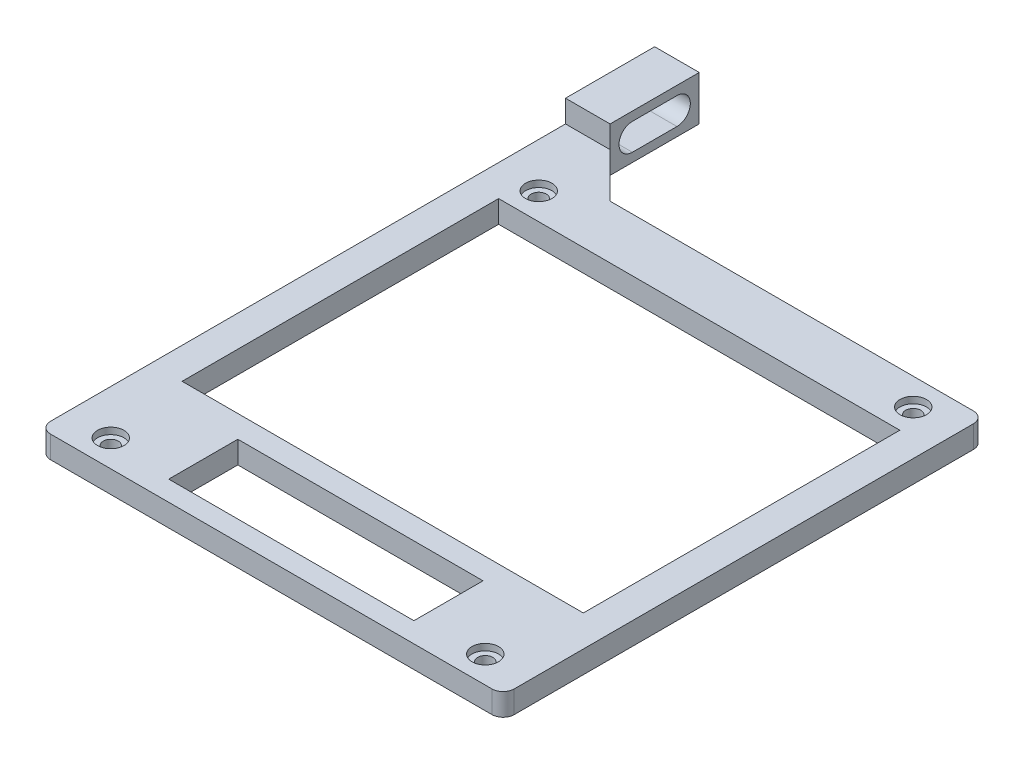
SolidWorks part; units mm, degrees
ref_plane "Front Plane" through (0, 0, 0) normal (0, 0, 1) x (1, 0, 0)
ref_plane "Top Plane" through (0, 0, 0) normal (0, 1, 0) x (1, 0, 0)
ref_plane "Right Plane" through (0, 0, 0) normal (1, 0, 0) x (0, 0, -1)
sketch "Sketch1" plane through (0, 0, 0) normal (0, 1, 0) x (1, 0, 0)
  line L1 (0, 0) -> (132.08, 0)
  line L2 (0, 0) -> (0, 137.16)
  line L3 (0, 137.16) -> (132.08, 137.16)
  line L4 (132.08, 0) -> (132.08, 137.16)
  dimension "D1" = 132.08
  dimension "D2" = 137.16
extrude "Boss-Extrude1" add sketch "Sketch1" along normal blind 6.35
ref_axis "Axis1" through (66.04, 6.35, 0) along (0, 0, -1)
ref_axis "Axis2" through (0, 6.35, -68.58) along (1, 0, 0)
hole_wizard "CBORE for #6 Button Head Cap Screw1" positions "Sketch4" profile "Sketch3" counterbore size "#6" standard "ANSI Inch" end condition up to next
sketch "Sketch4" plane through (0, 6.35, 0) normal (0, 1, 0) x (1, 0, 0)
  line L0 (12.7, 129.54) -> (119.38, 129.54)
  line L1 (119.38, 129.54) -> (119.38, 7.62)
  line L2 (119.38, 7.62) -> (12.7, 7.62)
  line L4 (12.7, 129.54) -> (12.7, 7.62)
  line L7 (66.04, 0) -> (66.04, 137.16) construction
  line L8 (0, 68.58) -> (132.08, 68.58) construction
  point P0 (12.7, 129.54)
  point P2 (119.38, 129.54)
  point P4 (119.38, 7.62)
  point P6 (12.7, 7.62)
  point P28 (66.04, 129.54)
  point P31 (119.38, 68.58)
  dimension "D1" = 106.68
  dimension "D2" = 121.92
sketch "Sketch3" plane through (12.7, 6.35, -129.54) normal (1, 0, 0) x (0, 0, 1)
  line L0 (0, 0) -> (0, 6.35)
  line L1 (0, 6.35) -> (2.1526, 6.35)
  line L3 (2.1526, 6.35) -> (2.1527, 1.8542)
  line L4 (2.1527, 1.8542) -> (3.7706, 1.8542)
  line L5 (3.7706, 1.8542) -> (3.7706, 0)
  line L7 (3.7706, 0) -> (0, 0)
  line L11 (0, -6.35) -> (0, 107.95) construction
  dimension "Thru Hole Dia." = 4.3053
  dimension "Thru Hole Depth" = 6.35
  dimension "C'Bore Dia." = 7.5413
  dimension "C'Bore Depth" = 1.8542
sketch "Sketch5" plane through (0, 6.35, 0) normal (0, 1, 0) x (1, 0, 0)
  line L0 (0, 68.58) -> (132.08, 68.58) construction
  line L1 (8.89, 15.24) -> (123.19, 15.24)
  line L2 (8.89, 15.24) -> (8.89, 121.92)
  line L3 (8.89, 121.92) -> (123.19, 121.92)
  line L4 (123.19, 15.24) -> (123.19, 121.92)
  line L5 (8.89, 15.24) -> (123.19, 121.92) construction
  line L6 (8.89, 121.92) -> (123.19, 15.24) construction
  line L7 (66.04, 0) -> (66.04, 137.16) construction
  point P0 (66.04, 68.58)
  dimension "D1" = 114.3
  dimension "D2" = 106.68
extrude "Cut-Extrude1" cut sketch "Sketch5" against normal through all
sketch "Sketch6" plane through (0, 0, 0) normal (0, -1, 0) x (-1, 0, 0)
  line L1 (0, 137.16) -> (-12.7, 137.16)
  line L2 (0, 137.16) -> (0, 175.26)
  line L3 (0, 175.26) -> (-12.7, 175.26)
  line L4 (-12.7, 137.16) -> (-12.7, 175.26)
  dimension "D1" = 12.7
  dimension "D2" = 38.1
extrude "Boss-Extrude2" add sketch "Sketch6" against normal blind 6.35
sketch "Sketch7" plane through (0, 0, -175.26) normal (0, 0, -1) x (-1, 0, 0)
  line L4 (0, 6.35) -> (-12.7, 6.35)
  line L5 (0, 6.35) -> (0, 12.7)
  line L6 (0, 12.7) -> (-12.7, 12.7)
  line L7 (-12.7, 6.35) -> (-12.7, 12.7)
  dimension "D1" = 6.35
extrude "Boss-Extrude3" add sketch "Sketch7" against normal blind 25.4
sketch "Sketch8" plane through (0, 0, 0) normal (-1, 0, 0) x (0, 0, 1)
  line L0 (-175.26, 6.35) -> (-149.86, 6.35)
  line L1 (-175.26, 12.7) -> (-175.26, 0) construction
  line L3 (-168.91, 6.35) -> (-156.21, 6.35) construction
  line L4 (-168.91, 10.16) -> (-156.21, 10.16)
  line L5 (-168.91, 2.54) -> (-156.21, 2.54)
  arc A0 (-168.91, 10.16) -> (-168.91, 2.54) centre (-168.91, 6.35) ccw
  arc A1 (-156.21, 2.54) -> (-156.21, 10.16) centre (-156.21, 6.35) ccw
  point P8 (-162.56, 6.35)
  dimension "D1" = 3.81
  dimension "D2" = 6.35
extrude "Cut-Extrude2" cut sketch "Sketch8" against normal up to next contours L5 A1 L0 A0 | L0 A1 L4 A0 region at (0, 8.1628, -162.56) region at (0, 4.5372, -162.56)
ref_axis "Axis3" through (12.7, 6.35, -162.56) along (-1, 0, 0)
ref_axis "Axis4" through (12.7, 6.35, -156.21) along (-1, 0, 0)
chamfer "Chamfer1" distance 12.7 angle 45 1 edges at (12.7, 3.175, -137.16)
sketch "Sketch9" plane through (0, 6.35, 0) normal (0, 1, 0) x (1, 0, 0)
  line L7 (66.04, 15.24) -> (66.04, 0) construction
  line L8 (8.89, 15.24) -> (123.19, 15.24) construction
  line L9 (0, 0) -> (132.08, 0) construction
  line L10 (100.965, 15.24) -> (31.115, 15.24)
  line L11 (31.115, 15.24) -> (31.115, 5.715)
  line L12 (31.115, 5.715) -> (100.965, 5.715)
  line L13 (100.965, 15.24) -> (100.965, 5.715)
  point P10 (66.04, 5.715)
  dimension "D1" = 34.925
  dimension "D2" = 9.525
extrude "Cut-Extrude3" cut sketch "Sketch9" against normal up to next
fillet "Fillet1" radius 3.175 3 edges at (132.08, 3.175, -137.16) (132.08, 3.175, 0) (0, 3.175, 0)
sketch "Sketch11" plane through (0, 6.35, 0) normal (0, 1, 0) x (1, 0, 0)
  line L3 (31.115, 5.715) -> (100.965, 5.715) construction
  line L4 (31.115, 15.24) -> (31.115, 5.715) construction
  line L5 (8.89, 15.24) -> (31.115, 15.24)
  line L6 (100.965, 15.24) -> (123.19, 15.24)
  line L7 (100.965, 15.24) -> (100.965, 25.4) construction
  line L8 (31.115, 5.715) -> (100.965, 5.715) construction
  line L9 (31.115, 25.4) -> (31.115, 15.24) construction
  line L10 (31.115, 15.24) -> (100.965, 15.24) construction
  line L11 (31.115, 25.4) -> (100.965, 25.4)
  line L15 (8.89, 121.92) -> (8.89, 15.24) construction
  line L16 (123.19, 15.24) -> (123.19, 121.92) construction
  line L17 (8.89, 31.75) -> (123.19, 31.75)
  line L18 (31.115, 25.4) -> (31.115, 15.24)
  line L19 (100.965, 15.24) -> (100.965, 25.4)
  line L20 (123.19, 15.24) -> (123.19, 31.75)
  line L21 (8.89, 15.24) -> (8.89, 31.75)
  point P9 (0, 0)
  point P16 (0, 0)
  point P17 (0, 0)
  point P21 (0, 0)
  dimension "D1" = 6.35
  dimension "D2" = 10.16
extrude "Boss-Extrude4" add sketch "Sketch11" against normal up to surface (6.35 mm away) up to face at (66.04, 0, -39.5288)
